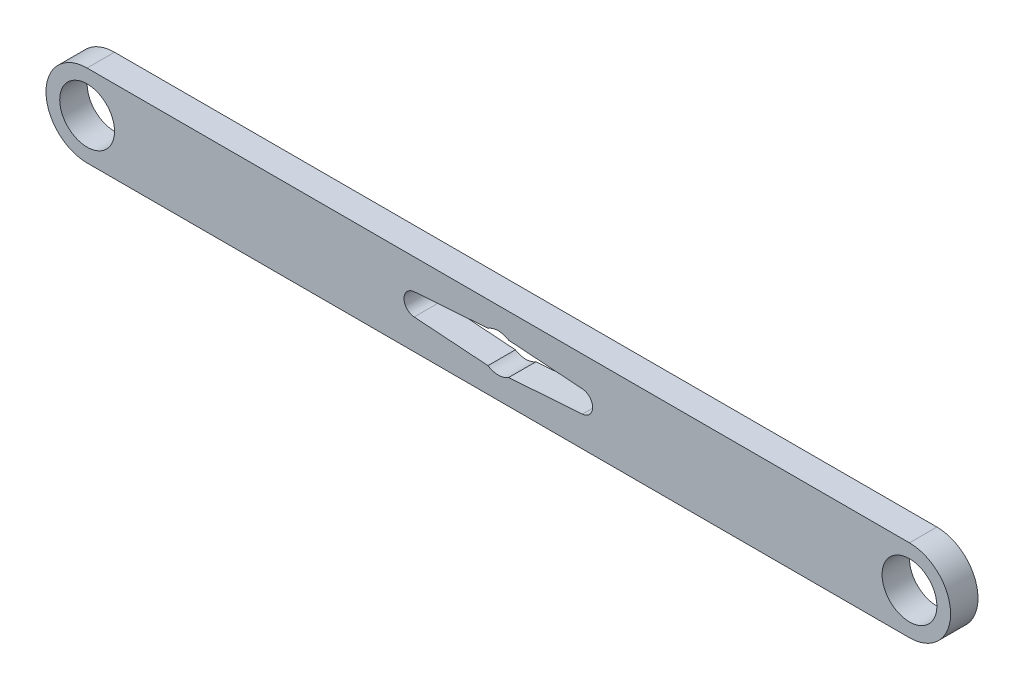
SolidWorks part; units mm, degrees
material "Acrylic (Medium-high impact)"
ref_plane "Front Plane" through (0, 0, 0) normal (0, 0, 1) x (1, 0, 0)
ref_plane "Top Plane" through (0, 0, 0) normal (0, 1, 0) x (1, 0, 0)
ref_plane "Right Plane" through (0, 0, 0) normal (1, 0, 0) x (0, 0, -1)
sketch "Sketch1" plane through (0, 0, 0) normal (0, 0, 1) x (1, 0, 0)
  line L0 (75, 0) -> (-75, 0) construction
  line L1 (75, -7.5) -> (-75, -7.5)
  line L2 (75, 7.5) -> (-75, 7.5)
  line L3 (-1.8835, 2.95) -> (-15.3416, 1.995)
  line L5 (0, 3.5) -> (0, -3.5) construction
  line L11 (-1.8835, -2.95) -> (-15.3416, -1.995)
  line L12 (1.8835, -2.95) -> (15.3416, -1.995)
  line L13 (1.8835, 2.95) -> (15.3416, 1.995)
  arc A0 (75, -7.5) -> (75, 7.5) centre (75, 0) ccw
  arc A1 (-75, 7.5) -> (-75, -7.5) centre (-75, 0) ccw
  circle A2 centre (75, 0) radius 5
  circle A3 centre (-75, 0) radius 5
  arc A16 (-1.8835, -2.95) -> (1.8835, -2.95) centre (0, 0) ccw
  arc A17 (-15.3416, 1.995) -> (-15.3416, -1.995) centre (-15.2, 0) ccw
  arc A18 (15.3416, 1.995) -> (15.3416, -1.995) centre (15.2, 0) cw
  arc A19 (-1.8835, 2.95) -> (-3.5, 0) centre (0, 0) ccw construction
  arc A20 (-3.5, 0) -> (-1.8835, -2.95) centre (0, 0) ccw construction
  arc A21 (1.8835, -2.95) -> (3.5, 0) centre (0, 0) ccw construction
  arc A22 (1.8835, 2.95) -> (-1.8835, 2.95) centre (0, 0) ccw
  arc A23 (3.5, 0) -> (1.8835, 2.95) centre (0, 0) ccw construction
  point P2 (0, 0)
  point P25 (-17.2, 0)
  dimension "D2" = 10
  dimension "D8" = 2
  dimension "D4" = 10
  dimension "D6" = 5.9
  dimension "D7" = 17.2
  dimension "D5" = 7
  dimension "D1" = 150
  dimension "D3" = 15
extrude "Boss-Extrude1" add sketch "Sketch1" along normal blind 5
